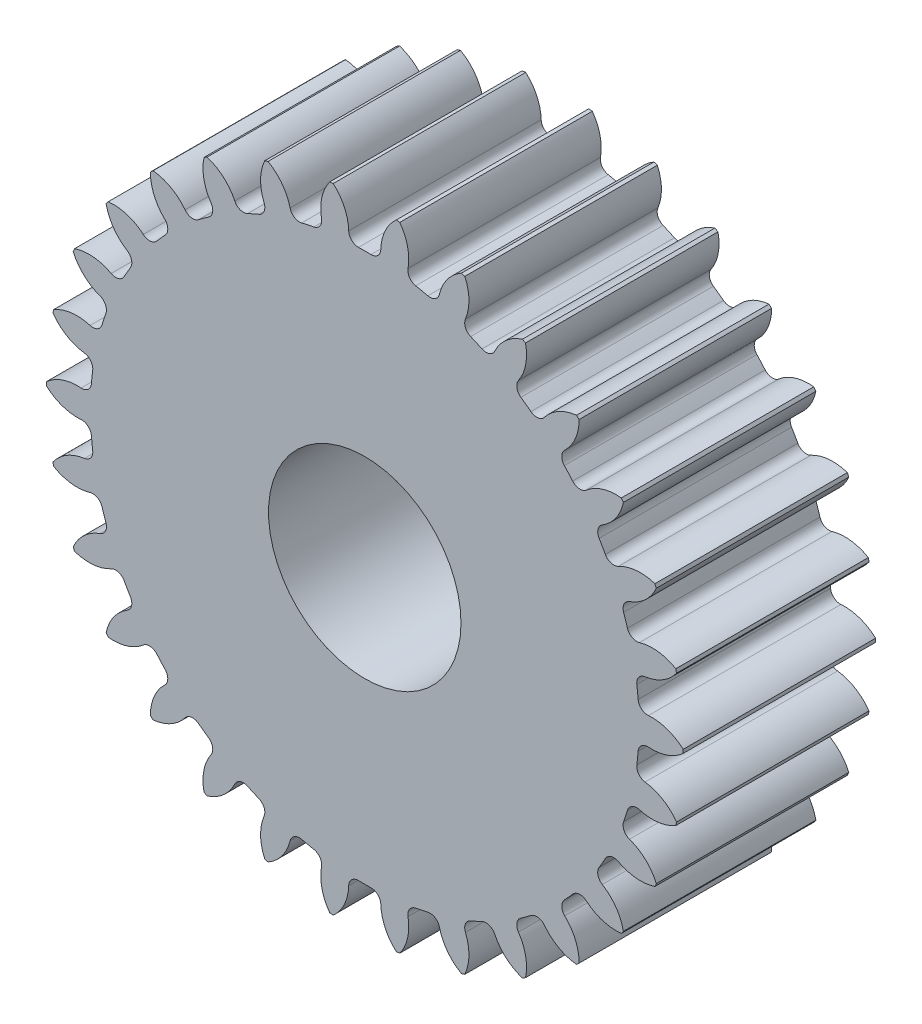
SolidWorks part; units mm, degrees
ref_plane "Front Plane" through (0, 0, 0) normal (0, 0, 1) x (1, 0, 0)
ref_plane "Top Plane" through (0, 0, 0) normal (0, 1, 0) x (1, 0, 0)
ref_plane "Right Plane" through (0, 0, 0) normal (1, 0, 0) x (0, 0, -1)
sketch "Sketch1" plane through (0, 0, 0) normal (0, 0, 1) x (1, 0, 0)
  circle A0 centre (0, 0) radius 2
  circle A1 centre (0, 0) radius 6.6165
  dimension "D1" = 4
  dimension "D2" = 13.233
extrude "Boss-Extrude1" add sketch "Sketch1" along normal blind 4
sketch "Sketch2" plane through (0, 0, 4) normal (0, 0, 1) x (1, 0, 0)
  line L0 (0, 5.6996) -> (0, 6.6165) construction
  line L2 (-0.5367, 6.5947) -> (-0.6726, 6.9681) construction
  circle A0 centre (0, 0) radius 6.6165 construction
  arc A2 (0.3499, 5.6888) -> (-0.3499, 5.6888) centre (0, 0) ccw
  arc A3 (0.655, 6.584) -> (-0.655, 6.584) centre (0, 0) ccw
  arc A4 (-0.655, 6.584) -> (-0.3499, 5.6888) centre (-1.2945, 5.8665) cw
  arc A5 (0.655, 6.584) -> (0.3499, 5.6888) centre (1.2945, 5.8665) ccw
  point P7 (-0.6726, 6.9681)
  point P8 (-0.3499, 5.6996)
  dimension "D1" = 20
extrude "Cut-Extrude1" cut sketch "Sketch2" against normal blind 13
fillet "Fillet3" radius 0.2 2 edges at (0.3499, 5.6888, 2) (-0.3499, 5.6888, 2)
pattern_circular "CirPattern5" count 30 over 360 about axis through (0, 0, 4) along (0, 0, 1) of "Fillet3", "Cut-Extrude1"
